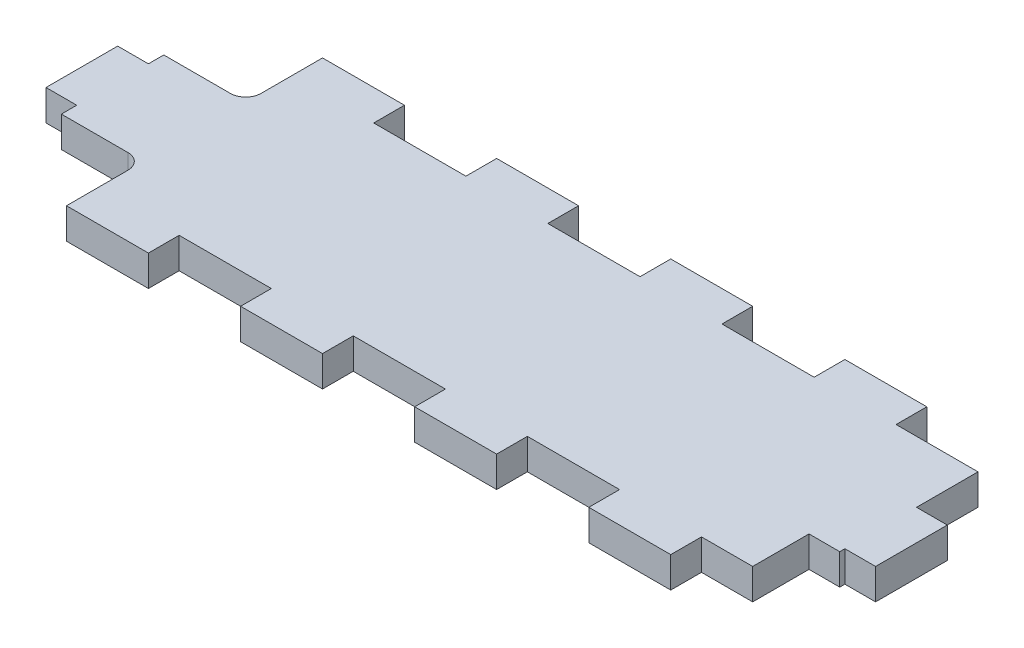
SolidWorks part; units mm, degrees
ref_plane "Front Plane" through (0, 0, 0) normal (0, 0, 1) x (1, 0, 0)
ref_plane "Top Plane" through (0, 0, 0) normal (0, 1, 0) x (1, 0, 0)
ref_plane "Right Plane" through (0, 0, 0) normal (1, 0, 0) x (0, 0, -1)
sketch "Sketch1" plane through (0, 0, 0) normal (0, 1, 0) x (1, 0, 0)
  line L0 (-81, 0) -> (-71, 0) construction
  line L1 (-81, 25) -> (81, 25)
  line L2 (-81, 25) -> (-81, -25)
  line L3 (-81, -25) -> (81, -25)
  line L4 (81, 25) -> (81, -25)
  line L5 (-81, 25) -> (81, -25) construction
  line L6 (-81, -25) -> (81, 25) construction
  line L7 (-81, 25) -> (-71, 25)
  line L8 (-81, 25) -> (-81, -25)
  line L9 (-81, -25) -> (-71, -25)
  line L10 (-71, 25) -> (-71, -25)
  line L12 (-81, -10) -> (-71, -10)
  line L13 (-81, -10) -> (-81, 10)
  line L14 (-81, 10) -> (-71, 10)
  line L15 (-71, -10) -> (-71, 10)
  line L16 (-81, -10) -> (-71, 10) construction
  line L17 (-81, 10) -> (-71, -10) construction
  point P0 (0, 0)
  point P10 (-76, 0)
  dimension "D3" = 10
  dimension "D4" = 20
  dimension "D2" = 50
  dimension "D1" = 162
sketch "Sketch2" plane through (0, 0, 0) normal (0, 0, 1) x (1, 0, 0)
  line L0 (0, 0) -> (0, 6) construction
  line L1 (-81, 0) -> (81, 0) construction
extrude "Boss-Extrude1" add sketch "Sketch1" along normal up to vertex (6 mm away) contours L2 L3 L4 L1 up to point (0, 6, 0)
sketch "Sketch3" plane through (0, 6, 0) normal (0, 1, 0) x (1, 0, 0)
  line L0 (-81, 25) -> (-81, -25) construction
  line L1 (-81, 10) -> (-59, 10) construction
  line L2 (-81, 10) -> (-81, -10) construction
  line L3 (-81, -10) -> (-59, -10) construction
  line L4 (-59, 10) -> (-59, -10) construction
  line L5 (-59, 19.2244) -> (-59, -19.2244) construction
  line L6 (0, 0) -> (-59, 0) construction
  line L7 (-81, 19) -> (-75, 19) construction
  line L8 (-81, -25) -> (-59, -25) construction
  line L9 (-81, -25) -> (-81, -19) construction
  line L10 (-81, -19) -> (-59, -19) construction
  line L11 (-59, -25) -> (-59, -19) construction
  line L12 (-81, 25) -> (-59, 25) construction
  line L13 (-81, 25) -> (-81, 19) construction
  line L14 (-81, 19) -> (-59, 19) construction
  line L15 (-59, 25) -> (-59, 19) construction
  line L16 (-75, 19) -> (-75, 10) construction
  line L18 (-75, 19) -> (-59, 19)
  line L19 (-75, 19) -> (-75, 10)
  line L20 (-75, 10) -> (-59, 10)
  line L21 (-59, 19) -> (-59, 10)
  line L22 (-59, -10) -> (-75, -10)
  line L23 (-59, -10) -> (-59, -19)
  line L24 (-59, -19) -> (-75, -19)
  line L25 (-75, -10) -> (-75, -19)
  dimension "D1" = 20
  dimension "D2" = 6
  dimension "D3" = 22
extrude "Cut-Extrude1" cut sketch "Sketch3" against normal through all
sketch "Sketch4" plane through (0, 6, 0) normal (0, 1, 0) x (1, 0, 0)
  line L0 (-59, -19) -> (-59, -25)
  line L1 (-81, -25) -> (81, -25) construction
  line L2 (-59, 19) -> (-59, 25)
  line L3 (-81, 25) -> (81, 25) construction
  line L4 (-59, 19) -> (-75, 19)
  line L5 (-75, 19) -> (-75, 7)
  line L6 (-75, 7) -> (-81, 7)
  line L7 (-81, 7) -> (-81, -7)
  line L8 (81, 25) -> (-81, 25)
  line L9 (-81, 25) -> (-81, -25)
  line L10 (-81, -25) -> (81, -25)
  line L11 (81, -25) -> (81, 25)
  line L12 (81, 25) -> (-81, 25)
  line L13 (-81, 25) -> (-81, -25)
  line L14 (-81, -25) -> (81, -25)
  line L15 (81, -25) -> (81, 25)
  line L16 (-81, -7) -> (-75, -7)
  line L17 (-75, -7) -> (-75, -19)
  line L18 (-75, -19) -> (-59, -19)
  line L19 (-75, 10) -> (-59, 10) construction
  line M10 (-59, -19) -> (-75, -19)
  line M11 (-75, -19) -> (-75, -10)
  line M12 (-75, 19) -> (-59, 19)
  line M15 (-75, 10) -> (-75, 19)
  line M16 (81, 25) -> (-81, 25)
  line M17 (-81, 25) -> (-81, -25)
  line M18 (-81, -25) -> (81, -25)
  dimension "D2" = 3
  dimension "D1" = 0
extrude "Cut-Extrude2" cut sketch "Sketch4" against normal through all contours L6 L5 L2 M15 M12 M16 M17 | L17 L16 L0 M17 M18 M10 M11 region at (-59.2843, 6, 22) region at (-80.7157, 6, -16)
sketch "Sketch6" plane through (0, 6, 0) normal (0, 1, 0) x (1, 0, 0)
  line L0 (-59, -25) -> (81, -25) construction
  line L1 (-43, -19) -> (-59, -19) construction
  line L2 (-43, -19) -> (-43, -25)
  line L3 (-43, -25) -> (-59, -25)
  line L4 (-59, -19) -> (-59, -25)
  line L5 (-25, -19) -> (-9, -19) construction
  line L6 (-25, -19) -> (-25, -25)
  line L7 (-25, -25) -> (-9, -25)
  line L8 (-9, -19) -> (-9, -25)
  line L9 (-9, -19) -> (-9, -25) construction
  line L10 (75, -25) -> (-75, -25) construction
  line L11 (-43, -19) -> (-25, -19)
  line L12 (-43, -19) -> (-43, -25)
  line L13 (-43, -25) -> (-25, -25)
  line L14 (-25, -19) -> (-25, -25)
  line L15 (-9, -19) -> (0, -19)
  line L16 (-9, -19) -> (-9, -25)
  line L17 (-9, -25) -> (0, -25)
  line L18 (0, -19) -> (0, -25)
  line M11 (-59, -25) -> (81, -25)
extrude "Cut-Extrude3" cut sketch "Sketch6" against normal through all contours L11 L2 L6 M11 | L18 L15 L8 M11 region at (-34, 6, 22) region at (-4.5, 6, 22)
mirror "Mirror1" about plane through (0, 0, 0) normal (0, 0, 1) of "Cut-Extrude3"
mirror "Mirror2" about plane through (0, 0, 0) normal (1, 0, 0) of "Mirror1"
sketch "Sketch7" plane through (0, 6, 0) normal (0, 1, 0) x (1, 0, 0)
  line L0 (81, 25) -> (81, -25) construction
  line L1 (59, -19) -> (81, -19)
  line L2 (59, -19) -> (59, -25)
  line L3 (59, -25) -> (81, -25)
  line L4 (81, -19) -> (81, -25)
  line L5 (81, -7) -> (75, -7)
  line L6 (81, -7) -> (81, -25)
  line L7 (81, -25) -> (75, -25)
  line L8 (75, -7) -> (75, -25)
  line L9 (-81, -7) -> (-75, -7) construction
  line M7 (43, -25) -> (81, -25)
  line M8 (81, -25) -> (81, 25)
extrude "Cut-Extrude4" cut sketch "Sketch7" against normal through all contours L8 L1 L2 M7 | L1 L8 L3 M8 | L5 L8 L1 M8 region at (67, 6, 22) region at (78, 6, 13) region at (78, 6, 22)
mirror "Mirror3" about plane through (0, 0, 0) normal (0, 0, 1) of "Cut-Extrude4"
fillet "Fillet1" radius 3 2 edges at (-59, 3, -10) (-59, 3, 10)
sketch "Sketch8" plane through (0, 6, 0) normal (0, 1, 0) x (1, 0, 0)
  line L0 (59, -19) -> (75, -19) construction
  line L1 (69, -19) -> (75, -19)
  line L2 (69, -19) -> (69, -8)
  line L3 (69, -8) -> (75, -8)
  line L4 (75, -19) -> (75, -8)
  line L5 (75, -7) -> (75, -19) construction
  line L7 (-75, -10) -> (-69, -10) construction
  line L8 (-75, -10) -> (-75, -21) construction
  line L9 (-75, -21) -> (-69, -21) construction
  line L10 (-69, -10) -> (-69, -21) construction
extrude "Cut-Extrude5" cut sketch "Sketch8" against normal through all
equation "\"glass_width\"= 150"
equation "\"glass_height\"= 100"
equation "\"glass_thickness\"= 4"
equation "\"brood_space\"= 42"
equation "\"t1\"= 6"
equation "\"t2\"= 6"
equation "\"box_depth\"= \"brood_space\" + \"glass_thickness\" + \"glass_thickness\" + \"t2\" + \"t2\""
equation "\"box_width\"= \"glass_width\" + \"t1\" + \"t1\""
equation "\"food_height\"= 70"
equation "\"box_height\"= \"glass_height\" + ( \"t1\" * 3 ) + \"food_height\""
equation "\"D1@Sketch2\"=\"t1\""
equation "\"entry_height\"= 24"
equation "\"entry_diameter\"= 8"
equation "\"food_top_clearance\"= 10"
equation "\"bar_width\"= 20"
equation "\"glassblocker_lower_height\"= 10"
equation "\"D2@Sketch1\"=\"brood_space\"+\"glass_thickness\"+\"glass_thickness\""
equation "\"D2@Sketch3\"=\"t1\""
equation "\"D1@Sketch1\"=\"box_width\""
